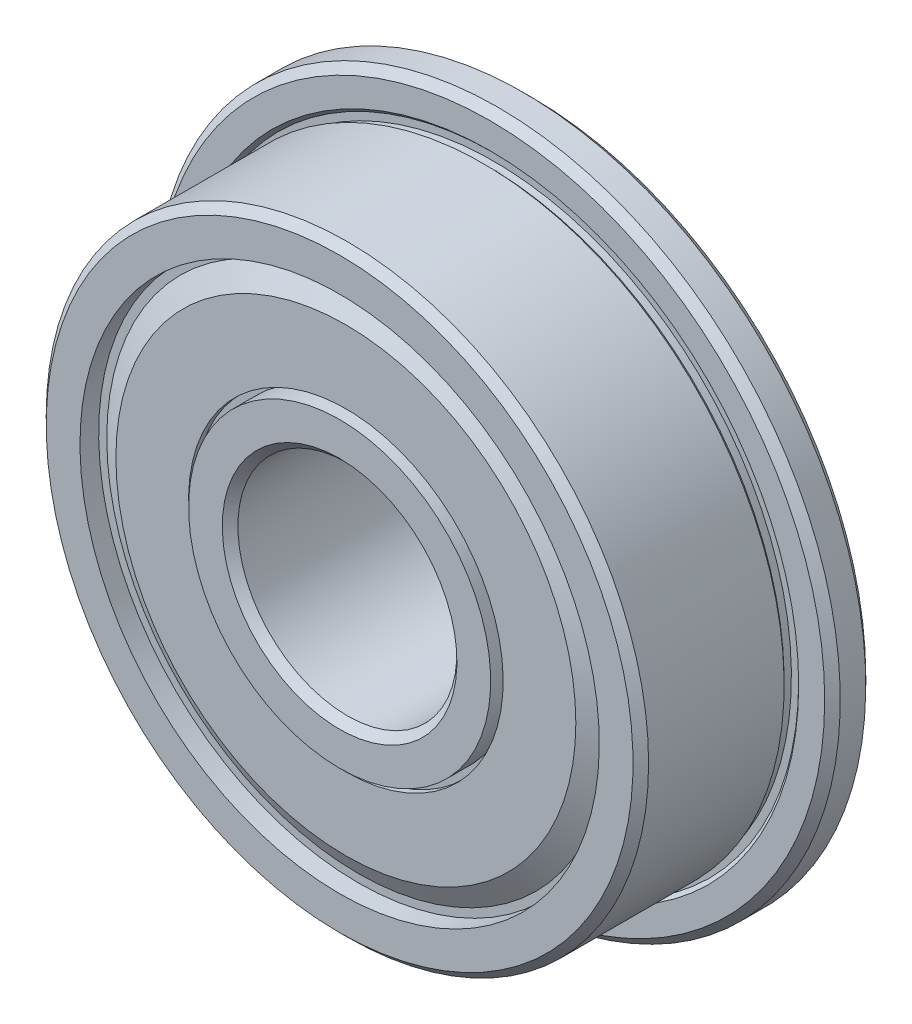
SolidWorks part; units mm, degrees
ref_plane "Front Plane" through (0, 0, 0) normal (0, 0, 1) x (1, 0, 0)
ref_plane "Top Plane" through (0, 0, 0) normal (0, 1, 0) x (1, 0, 0)
ref_plane "Right Plane" through (0, 0, 0) normal (1, 0, 0) x (0, 0, -1)
sketch "Sketch1" plane through (0, 0, 0) normal (1, 0, 0) x (0, 0, -1)
  line L0 (0, 11) -> (0, -11) construction
  line L1 (-3.5, 11) -> (3.5, 11) construction
  line L2 (0, 0) -> (3.5, 0) construction
  line L3 (3.5, 12.5) -> (3.5, -12.5) construction
  line L4 (3.5, -12.5) -> (2, -12.5) construction
  line L5 (3.5, 4) -> (0, 4) construction
  line L6 (3.5, 4) -> (3.5, -4) construction
  dimension "OD" = 22
  dimension "Width" = 7
  dimension "Flange Thickness" = 1.5
  dimension "ID" = 8
  dimension "Flange OD" = 25
sketch "Sketch2" plane through (0, 0, 0) normal (1, 0, 0) x (0, 0, -1)
  line L0 (3.5, 12.5) -> (2, 12.5)
  line L1 (2, 12.5) -> (2, 11.2652)
  line L2 (1.7348, 11) -> (-3.5, 11)
  line L3 (-3.5, 11) -> (-3.5, 8.725)
  line L4 (-3.5, 8.725) -> (-1.5613, 8.725)
  line L5 (3.5, 12.5) -> (3.5, -12.5) construction
  line L6 (3.5, 8.725) -> (3.5, 12.5)
  line L7 (3.5, 4) -> (-3.5, 4)
  line L8 (-3.5, 4) -> (-3.5, 6.275)
  line L9 (-3.5, 6.275) -> (-1.5613, 6.275)
  line L10 (3.5, 6.275) -> (3.5, 4)
  line L11 (0, 11) -> (0, 4) construction
  line L12 (-1.9845, 7.5) -> (1.9845, 7.5) construction
  line L13 (1.5613, 8.725) -> (3.5, 8.725)
  line L14 (1.5613, 6.275) -> (3.5, 6.275)
  line L15 (2, 11.2652) -> (2.1326, 11.1326)
  line L16 (2.1326, 11.1326) -> (2.1326, 10.8674)
  line L17 (2.1326, 10.8674) -> (1.8674, 10.8674)
  line L18 (1.8674, 10.8674) -> (1.7348, 11)
  line L19 (2, 11) -> (2.1326, 10.8674) construction
  line L20 (2.1326, 11.1326) -> (1.8674, 10.8674) construction
  line L21 (1.7348, 11) -> (2, 11) construction
  line L22 (2, 11) -> (2, 11.2652) construction
  line L23 (-3.5, 0) -> (3.5, 0) construction
  circle A0 centre (0, 7.5) radius 1.9845 construction
  arc A1 (-1.5613, 8.725) -> (1.5613, 8.725) centre (0, 7.5) cw
  arc A2 (-1.5613, 6.275) -> (1.5613, 6.275) centre (0, 7.5) ccw
  dimension "Ball Dia." = 3.969
  dimension "D2" = 135
  dimension "D3" = 0.375
  dimension "Race Thikness" = 2.275
  dimension "D4" = 2.45
revolve "Revolve1" add sketch "Sketch2" angle 360 about L2
fillet "Fillet1" radius 0.2844 3 edges at (0, -12.5, -3.5) (0, -12.5, -2) (0, -11, 3.5) profile chamfer
sketch "Sketch3" plane through (0, 0, 0) normal (0, 0, 1) x (1, 0, 0)
  line L0 (-4, 0) -> (4, 0) construction
  line L1 (-11, 0) -> (11, 0) construction
  point P5 (0, 0)
  dimension "ID2" = 8
  dimension "OD2" = 22
fillet "Fillet2" radius 0.2844 2 edges at (0, -4, -3.5) (0, -4, 3.5) profile chamfer
sketch "Sketch7" plane through (0, 0, 0) normal (0, 0, 1) x (1, 0, 0)
  line L0 (0, 9.4845) -> (0, 5.5155)
  line L1 (0, 12.5) -> (0, -12.5) construction
  line L2 (-2.6024, 9.4845) -> (0, 0) construction
  line L3 (0, 0) -> (2.6024, 9.4845) construction
  line L4 (2.6024, 9.4845) -> (-2.6024, 9.4845) construction
  circle A0 centre (0, 7.5) radius 1.9845 construction
  circle A1 centre (0, 0) radius 9.4845 construction
  circle A2 centre (0, 0) radius 5.5155 construction
  arc A4 (0, 9.4845) -> (0, 5.5155) centre (0, 7.5) ccw
  dimension "D1" = 30.686
revolve "Revolve3" add sketch "Sketch7" angle 360 about L0
pattern_circular "CirPattern3" count 8 over 360 about axis through (0, 0, 0) along (0, 0, -1) of bodies 107
sketch "Sketch8" plane through (0, 0, 0) normal (1, 0, 0) x (0, 0, -1)
  line L1 (-3.5, 8.725) -> (-2.59, 8.725)
  line L2 (-3.5, 8.725) -> (-3.5, 9.4833)
  line L3 (-3.5, 9.4833) -> (-2.59, 9.4833)
  line L4 (-2.59, 8.725) -> (-2.59, 9.4833)
  line L5 (3.5, 8.725) -> (2.59, 8.725)
  line L6 (3.5, 8.725) -> (3.5, 9.4833)
  line L7 (3.5, 9.4833) -> (2.59, 9.4833)
  line L8 (2.59, 8.725) -> (2.59, 9.4833)
  line L9 (3.5, 6.275) -> (2.59, 6.275)
  line L10 (3.5, 6.275) -> (3.5, 5.5167)
  line L11 (3.5, 5.5167) -> (2.59, 5.5167)
  line L12 (2.59, 6.275) -> (2.59, 5.5167)
  line L13 (-3.5, 6.275) -> (-2.59, 6.275)
  line L14 (-3.5, 6.275) -> (-3.5, 5.5167)
  line L15 (-3.5, 5.5167) -> (-2.59, 5.5167)
  line L16 (-2.59, 6.275) -> (-2.59, 5.5167)
  dimension "D1" = 0.7583
  dimension "D2" = 0.91
revolve "Cut-Revolve1" cut sketch "Sketch8" angle 360 about L2
sketch "Sketch9" plane through (0, 0, 0) normal (1, 0, 0) x (0, 0, -1)
  line L0 (-2.59, 9.4833) -> (-2.59, 9.1262)
  line L1 (-2.59, 9.1262) -> (-3.045, 8.3381)
  line L2 (-3.045, 8.3381) -> (-3.045, 5.7442)
  line L3 (3.045, 5.7442) -> (3.045, 5.5167) construction
  line L4 (2.59, 9.4833) -> (2.59, 9.1262)
  line L5 (2.59, 9.1262) -> (3.045, 8.3381)
  line L6 (3.045, 8.3381) -> (3.045, 5.7442)
  line L7 (3.5, 5.5167) -> (2.59, 5.5167) construction
  line L8 (-2.8175, 9.4833) -> (-2.8175, 9.1871)
  line L9 (-2.8175, 9.1871) -> (-3.2725, 8.3991)
  line L10 (-3.2725, 8.3991) -> (-3.2725, 5.7442)
  line L11 (-2.59, 9.4833) -> (-2.8175, 9.4833)
  line L12 (-3.045, 5.7442) -> (-3.2725, 5.7442)
  line L13 (2.8175, 9.4833) -> (2.8175, 9.1871)
  line L14 (2.8175, 9.1871) -> (3.2725, 8.3991)
  line L15 (3.2725, 8.3991) -> (3.2725, 5.7442)
  line L16 (2.59, 9.4833) -> (2.8175, 9.4833)
  line L17 (3.045, 5.7442) -> (3.2725, 5.7442)
  line L18 (-2.59, 9.1262) -> (-2.59, 2.5308) construction
  line L19 (2.59, 9.1262) -> (2.59, 9.4833) construction
  line L20 (-2.59, 5.5167) -> (-3.5, 5.5167) construction
  line L22 (-3.045, 5.7442) -> (-3.045, 5.5167) construction
  dimension "D2" = 150
  dimension "D1" = 150
  dimension "D5" = 0.91
  dimension "D3" = 0.2275
  dimension "D4" = 0.2275
  dimension "D6" = 0.3571
revolve "Revolve4" add sketch "Sketch9" angle 360 about L2
equation "\"D1@Fillet1\"=\"Race Thikness@Sketch2\"/8"
equation "\"ID2@Sketch3\" = \"ID@Sketch1\""
equation "\"OD2@Sketch3\" = \"OD@Sketch1\""
equation "\"D1@Fillet2\"=\"Race Thikness@Sketch2\"/8"
equation "\"D1@CirPattern3\"=360/\"D1@Sketch7\"-4"
equation "\"D1@Sketch8\"=\"Race Thikness@Sketch2\"/3"
equation "\"D2@Sketch8\"=\"Race Thikness@Sketch2\"/2.5"
equation "\"D3@Sketch9\"=\"D5@Sketch9\"/4"
equation "\"D4@Sketch9\"=\"D5@Sketch9\"/4"
equation "\"D1@Sketch9\"=\"D2@Sketch9\""
equation "\"Ball Dia.@Sketch2\" = \"D1@Sketch2\"*.5"
equation "\"D4@Sketch2\"=((\"OD@Sketch1\"-\"ID@Sketch1\")/2)*.35"
